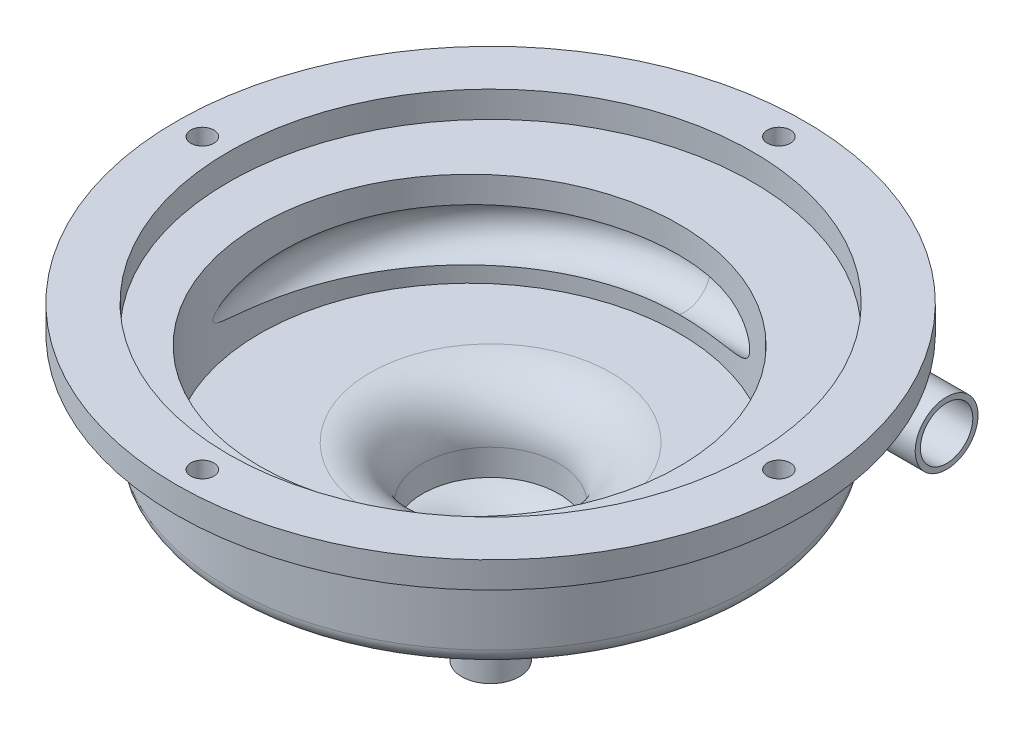
SolidWorks part; units mm, degrees
material "PLA"
ref_plane "Front Plane" through (0, 0, 0) normal (0, 0, 1) x (1, 0, 0)
ref_plane "Top Plane" through (0, 0, 0) normal (0, 1, 0) x (1, 0, 0)
ref_plane "Right Plane" through (0, 0, 0) normal (1, 0, 0) x (0, 0, -1)
sketch "Sketch1" plane through (0, 0, 0) normal (0, 1, 0) x (1, 0, 0)
  circle A0 centre (0, 0) radius 50
  circle A1 centre (0, -4) radius 40
  dimension "D1" = 4
  dimension "D2" = 80
extrude "Boss-Extrude1" add sketch "Sketch1" along normal blind 20
sketch "Sketch2" plane through (0, 0, 0) normal (0, 1, 0) x (1, 0, 0)
  circle A0 centre (0, 0) radius 50
  circle A1 centre (0, -4) radius 40
  dimension "D1" = 4
extrude "Boss-Extrude2" add sketch "Sketch2" along normal blind 2 and the other way blind 4 contours A1 region at (0, 0, 4)
sketch "Sketch3" plane through (0, 20, 0) normal (0, 1, 0) x (1, 0, 0)
  circle A0 centre (0, 0) radius 50
  circle A1 centre (0, 0) radius 60
  circle A2 centre (0, 55) radius 2.2
  circle A3 centre (55, 0) radius 2.2
  circle A4 centre (0, -55) radius 2.2
  circle A5 centre (-55, 0) radius 2.2
  point P15 (0, 0)
  dimension "D1" = 55
  dimension "D2" = 4
extrude "Boss-Extrude3" add sketch "Sketch3" along normal blind 5 separate body
ref_plane "Plane1" through (50, 0, 0) normal (1, 0, 0) x (0, 0, -1)
sketch "Sketch4" plane through (50, 0, 0) normal (1, 0, 0) x (0, 0, -1)
  line L0 (0, 0) -> (0, 36.7589) construction
  circle A2 centre (37, 10) radius 6
  circle A3 centre (37, 10) radius 4.75
  dimension "D1" = 12
  dimension "D2" = 9.5
  dimension "D5" = 37
  dimension "D6" = 10
  dimension "D3" = 10
  dimension "D4" = 37
sketch "Sketch5" plane through (0, 0, 0) normal (0, 1, 0) x (1, 0, 0)
  line L1 (0, 0) -> (66.027, 0) construction
  line L3 (50, 37) -> (19.8565, 37)
  point P0 (19.8565, 37)
sweep "Sweep1" add profiles "Sketch4" path "Sketch5"
sketch "Sketch6" plane through (0, 0, 0) normal (0, 1, 0) x (1, 0, 0)
  line L1 (50, -11) -> (50, 11) construction
  line L2 (50, 41) -> (50, 64.0091) construction
  line L3 (50, 41) -> (0, 41)
  arc A1 (0, 41) -> (-20.2102, -34.4256) centre (0, 0.5795) ccw
  dimension "D1" = 40.4205
  dimension "D2" = 20.2102
  dimension "D3" = 0.5795
sketch "Sketch7" plane through (50, 0, 0) normal (1, 0, 0) x (0, 0, -1)
  circle A2 centre (37, 10) radius 5
  dimension "D1" = 10
sweep "Cut-Sweep4" cut profiles "Sketch7" path "Sketch6"
sketch "Sketch9" plane through (0, -4, 0) normal (0, -1, 0) x (1, 0, 0)
  circle A0 centre (0, 0) radius 15
extrude "Boss-Extrude5" add sketch "Sketch9" along normal blind 15
sketch "Sketch10" plane through (0, -19, 0) normal (0, -1, 0) x (1, 0, 0)
  circle A0 centre (0, 0) radius 5.5
extrude "Boss-Extrude6" add sketch "Sketch10" along normal blind 15
sketch "Sketch11" plane through (0, -34, 0) normal (0, -1, 0) x (1, 0, 0)
  circle A0 centre (0, 0) radius 4.5
extrude "Cut-Extrude1" cut sketch "Sketch11" against normal through all
sketch "Sketch12" plane through (0, 2, 0) normal (0, 1, 0) x (1, 0, 0)
  circle A0 centre (0, 0) radius 13
extrude "Cut-Extrude2" cut sketch "Sketch12" against normal blind 15
fillet "Fillet1" radius 10 2 edges at (0, -13, 4.5) (0, 2, 13)
fillet "Fillet2" radius 3 3 edges at (0, -19, -15) (0, 0, 50) (0, -4, 44)
